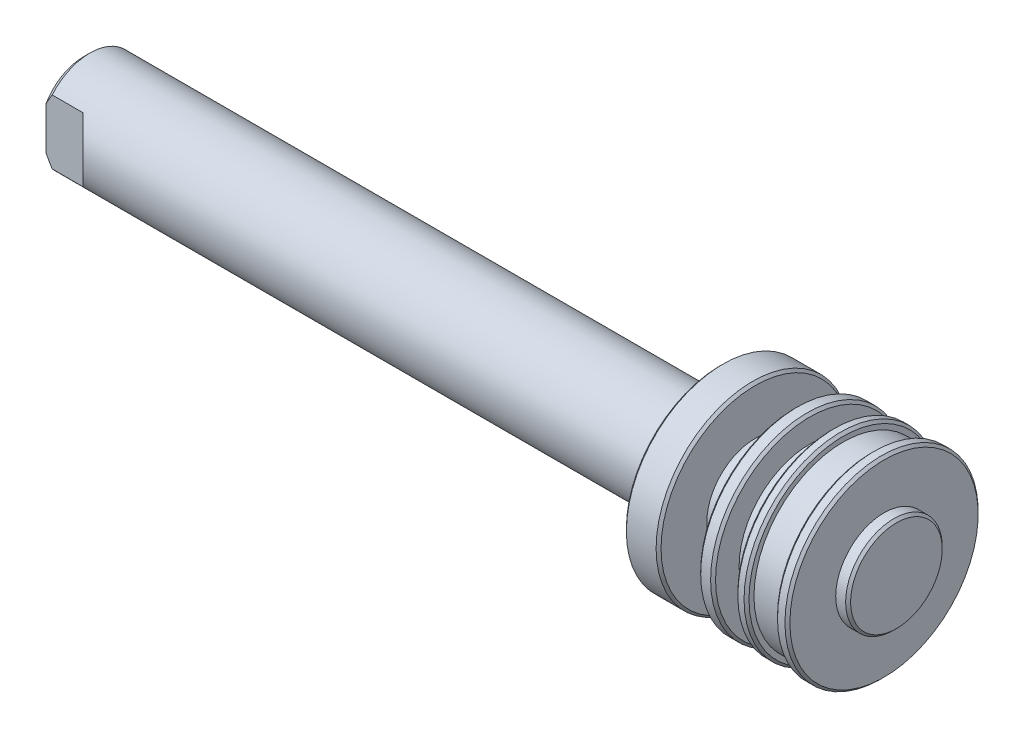
SolidWorks part; units mm, degrees
ref_plane "前视基准面" through (0, 0, 0) normal (0, 0, 1) x (1, 0, 0)
ref_plane "上视基准面" through (0, 0, 0) normal (0, 1, 0) x (1, 0, 0)
ref_plane "右视基准面" through (0, 0, 0) normal (1, 0, 0) x (0, 0, -1)
sketch "草图1" plane through (0, 0, 0) normal (0, 0, 1) x (1, 0, 0)
  line L0 (0, 0) -> (0, 3.5)
  line L1 (0, 3.5) -> (0.5, 4)
  line L2 (0.5, 4) -> (51.4, 4)
  line L3 (51.4, 4) -> (51.4, 7.6)
  line L4 (51.4, 7.6) -> (51.6, 7.8)
  line L5 (51.6, 7.8) -> (54, 7.8)
  line L6 (54, 7.8) -> (54.2, 7.6)
  line L7 (54.2, 7.6) -> (54.2, 3.9)
  line L8 (54.2, 3.9) -> (57.4, 3.9)
  line L9 (57.4, 3.9) -> (57.4, 7.6)
  line L10 (57.4, 7.6) -> (57.6, 7.8)
  line L11 (57.6, 7.8) -> (58.4, 7.8)
  line L12 (58.4, 7.8) -> (58.6, 7.6)
  line L13 (58.6, 7.6) -> (58.6, 5.7)
  line L14 (58.6, 5.7) -> (60.4, 5.7)
  line L15 (60.4, 5.7) -> (60.4, 7.6)
  line L16 (60.4, 7.6) -> (60.6, 7.8)
  line L17 (60.6, 7.8) -> (61.1, 7.8)
  line L18 (61.1, 7.8) -> (61.3, 7.6)
  line L19 (61.3, 7.6) -> (61.3, 7.2)
  line L20 (61.3, 7.2) -> (63.6, 7.2)
  line L21 (63.6, 7.2) -> (63.6, 7.6)
  line L22 (63.6, 7.6) -> (63.8, 7.8)
  line L23 (63.8, 7.8) -> (64.4, 7.8)
  line L24 (64.4, 7.8) -> (64.6, 7.6)
  line L25 (64.6, 7.6) -> (64.6, 3.9)
  line L26 (64.6, 3.9) -> (65.4, 3.9)
  line L27 (65.4, 3.9) -> (65.6, 3.7)
  line L28 (65.6, 3.7) -> (65.6, 0)
  line L29 (65.6, 0) -> (0, 0)
  line L30 (65.6, 0) -> (0, 0) construction
revolve "旋转1" add sketch "草图1" angle 360 about L30 reverse direction yes
sketch "草图2" plane through (0, 0, 0) normal (0, 0, 1) x (1, 0, 0)
  line L0 (0, 0) -> (0, 2)
  line L1 (0, 2) -> (0.379, 1.621)
  line L2 (0.379, 1.621) -> (10.8, 1.621)
  line L3 (10.8, 1.621) -> (11.7359, 0)
  line L4 (11.7359, 0) -> (0, 0)
  line L5 (11.7359, 0) -> (0, 0) construction
revolve "切除-旋转1" cut sketch "草图2" angle 360 about L5 reverse direction yes
cosmetic thread "装饰螺纹线1" parameters "D1"=9, "D2"=4
sketch "草图3" plane through (0, 0, 0) normal (0, 1, 0) x (1, 0, 0)
  line L0 (-9.2, -10.1211) -> (10.0711, -10.1211)
  line L1 (10.0711, -10.1211) -> (3, -3.05)
  line L2 (3, -3.05) -> (0, -3.05)
  line L3 (0, -3.05) -> (0, 3.05)
  line L4 (0, 3.05) -> (3, 3.05)
  line L5 (3, 3.05) -> (10.0711, 10.1211)
  line L6 (10.0711, 10.1211) -> (-9.2, 10.1211)
  line L7 (-9.2, 10.1211) -> (-9.2, -10.1211)
extrude "切除-拉伸1" cut sketch "草图3" along normal blind 8 and the other way blind 8
ref_plane "for_body XY" through (0, 0, 0) normal (1, 0, 0) x (0, 0, -1)
ref_plane "for_body XZ" through (0, 0, 0) normal (0, -1, 0) x (-1, 0, 0)
ref_plane "for_body YZ" through (0, 0, 0) normal (0, 0, -1) x (-1, 0, 0)
ref_axis "for_body X" through (0, 0, 80.9) along (0, 0, -1)
ref_axis "for_body Y" through (0, -50, 0) along (0, 1, 0)
ref_axis "for_body Z" through (80.9, 0, 0) along (-1, 0, 0)
sketch3d "for_body"
  point P0 (0, 0, 0)
